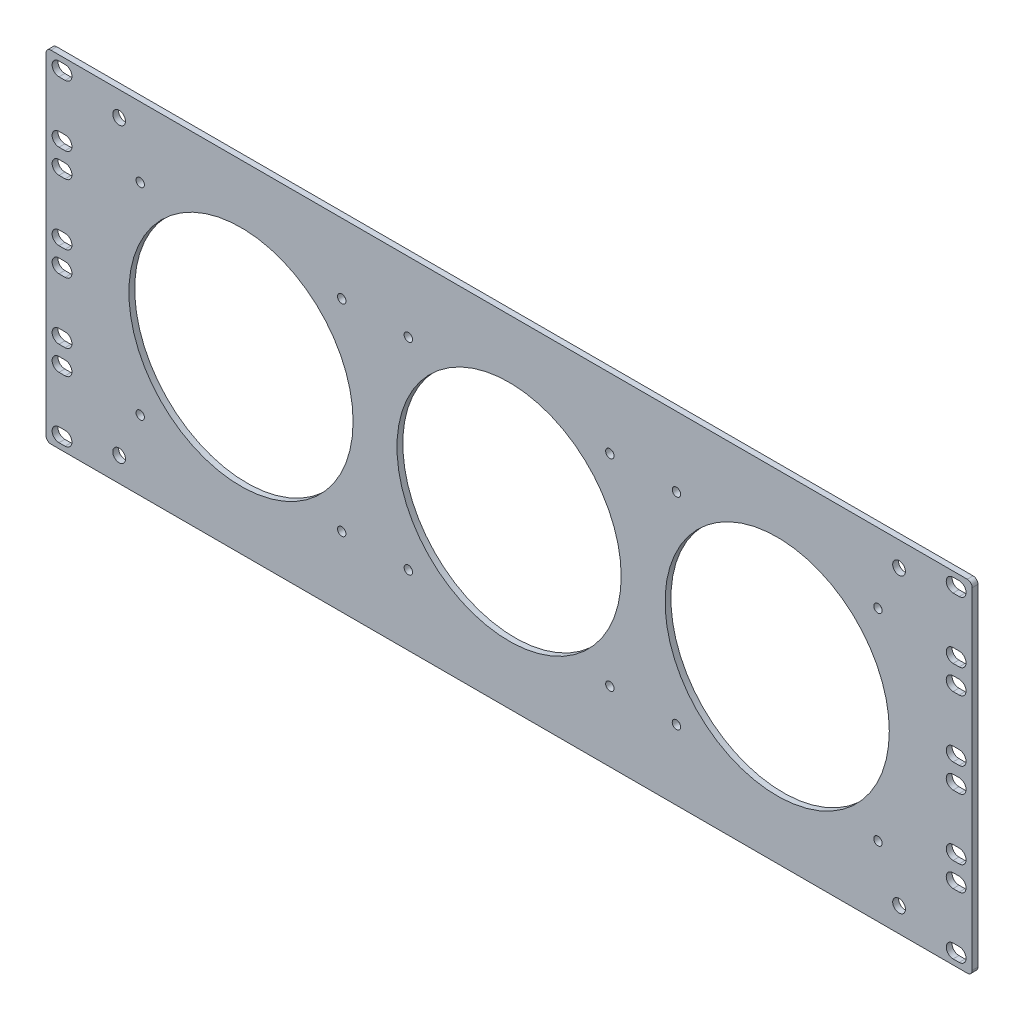
SolidWorks part; units mm, degrees
ref_plane "Plan de face" through (0, 0, 0) normal (0, 0, 1) x (1, 0, 0)
ref_plane "Plan de dessus" through (0, 0, 0) normal (0, 1, 0) x (1, 0, 0)
ref_plane "Plan de droite" through (0, 0, 0) normal (1, 0, 0) x (0, 0, -1)
sketch "Esquisse1" plane through (0, 0, 0) normal (0, 0, 1) x (1, 0, 0)
  line L1 (241.3, -88.9) -> (-241.3, -88.9)
  line L2 (241.3, -88.9) -> (241.3, 88.9)
  line L3 (241.3, 88.9) -> (-241.3, 88.9)
  line L4 (-241.3, -88.9) -> (-241.3, 88.9)
  line L5 (241.3, -88.9) -> (-241.3, 88.9) construction
  line L6 (241.3, 88.9) -> (-241.3, -88.9) construction
  point P0 (0, 0)
  dimension "D1" = 177.8
  dimension "D2" = 482.6
sheet metal parameters "Tôlerie 1" thickness 3.0378 parameters "D1"=0.0254, "Epaisseur"=3.0378
base flange "Tôle de base pliée1" sketch "Esquisse1" thickness 3.0378 reverse thickness direction no parameters "D1"=0.0254
sketch "Esquisse4" plane through (0, 0, 0) normal (0, 0, 1) x (1, 0, 0)
  line L0 (-234.5362, -82.55) -> (-231.3612, -82.55) construction
  line L1 (232.9487, -82.55) -> (-232.9487, -82.55) construction
  line L2 (232.9487, -82.55) -> (232.9487, 82.55) construction
  line L3 (232.9487, 82.55) -> (-232.9487, 82.55) construction
  line L4 (-232.9487, -82.55) -> (-232.9487, 82.55) construction
  line L5 (232.9487, -82.55) -> (-232.9487, 82.55) construction
  line L6 (232.9487, 82.55) -> (-232.9487, -82.55) construction
  line L7 (-234.5362, -78.9781) -> (-231.3612, -78.9781)
  line L8 (-234.5362, -86.1219) -> (-231.3612, -86.1219)
  line L9 (-234.5362, 82.55) -> (-231.3612, 82.55) construction
  line L10 (-234.5362, 86.1219) -> (-231.3612, 86.1219)
  line L11 (-234.5362, 78.9781) -> (-231.3612, 78.9781)
  line L12 (231.3612, 82.55) -> (234.5362, 82.55) construction
  line L13 (231.3612, 86.1219) -> (234.5362, 86.1219)
  line L14 (231.3612, 78.9781) -> (234.5362, 78.9781)
  line L15 (231.3612, -82.55) -> (234.5362, -82.55) construction
  line L16 (231.3612, -78.9781) -> (234.5362, -78.9781)
  line L17 (231.3612, -86.1219) -> (234.5362, -86.1219)
  line L18 (-234.5362, -38.1) -> (-231.3612, -38.1) construction
  line L19 (-234.5362, -34.5281) -> (-231.3612, -34.5281)
  line L20 (-234.5362, -41.6719) -> (-231.3612, -41.6719)
  line L21 (-234.5362, -50.8) -> (-231.3612, -50.8) construction
  line L22 (-234.5362, -47.2281) -> (-231.3612, -47.2281)
  line L23 (-234.5362, -54.3719) -> (-231.3612, -54.3719)
  line L24 (231.3612, -50.8) -> (234.5362, -50.8) construction
  line L25 (231.3612, -47.2281) -> (234.5362, -47.2281)
  line L26 (231.3612, -54.3719) -> (234.5362, -54.3719)
  line L27 (231.3612, -38.1) -> (234.5362, -38.1) construction
  line L28 (231.3612, -34.5281) -> (234.5362, -34.5281)
  line L29 (231.3612, -41.6719) -> (234.5362, -41.6719)
  line L30 (232.9487, -38.1) -> (232.9487, 82.55) construction
  line L31 (-234.5362, 6.35) -> (-231.3612, 6.35) construction
  line L32 (-234.5362, 9.9219) -> (-231.3612, 9.9219)
  line L33 (-234.5362, 2.7781) -> (-231.3612, 2.7781)
  line L34 (-234.5362, -6.35) -> (-231.3612, -6.35) construction
  line L35 (-234.5362, -2.7781) -> (-231.3612, -2.7781)
  line L36 (-234.5362, -9.9219) -> (-231.3612, -9.9219)
  line L37 (231.3612, 50.8) -> (234.5362, 50.8) construction
  line L38 (231.3612, 54.3719) -> (234.5362, 54.3719)
  line L39 (231.3612, 47.2281) -> (234.5362, 47.2281)
  line L40 (231.3612, 38.1) -> (234.5362, 38.1) construction
  line L41 (231.3612, 41.6719) -> (234.5362, 41.6719)
  line L42 (231.3612, 34.5281) -> (234.5362, 34.5281)
  line L43 (-234.5362, 50.8) -> (-231.3612, 50.8) construction
  line L44 (-234.5362, 54.3719) -> (-231.3612, 54.3719)
  line L45 (-234.5362, 47.2281) -> (-231.3612, 47.2281)
  line L46 (-234.5362, 38.1) -> (-231.3612, 38.1) construction
  line L47 (-234.5362, 41.6719) -> (-231.3612, 41.6719)
  line L48 (-234.5362, 34.5281) -> (-231.3612, 34.5281)
  line L49 (231.3612, 6.35) -> (234.5362, 6.35) construction
  line L50 (231.3612, 9.9219) -> (234.5362, 9.9219)
  line L51 (231.3612, 2.7781) -> (234.5362, 2.7781)
  line L52 (231.3612, -6.35) -> (234.5362, -6.35) construction
  line L53 (231.3612, -2.7781) -> (234.5362, -2.7781)
  line L54 (231.3612, -9.9219) -> (234.5362, -9.9219)
  arc A0 (-234.5362, -78.9781) -> (-234.5362, -86.1219) centre (-234.5362, -82.55) ccw
  arc A1 (-231.3612, -86.1219) -> (-231.3612, -78.9781) centre (-231.3612, -82.55) ccw
  arc A2 (-234.5362, 86.1219) -> (-234.5362, 78.9781) centre (-234.5362, 82.55) ccw
  arc A3 (-231.3612, 78.9781) -> (-231.3612, 86.1219) centre (-231.3612, 82.55) ccw
  arc A4 (231.3612, 86.1219) -> (231.3612, 78.9781) centre (231.3612, 82.55) ccw
  arc A5 (234.5362, 78.9781) -> (234.5362, 86.1219) centre (234.5362, 82.55) ccw
  arc A6 (231.3612, -78.9781) -> (231.3612, -86.1219) centre (231.3612, -82.55) ccw
  arc A7 (234.5362, -86.1219) -> (234.5362, -78.9781) centre (234.5362, -82.55) ccw
  arc A8 (-234.5362, -34.5281) -> (-234.5362, -41.6719) centre (-234.5362, -38.1) ccw
  arc A9 (-231.3612, -41.6719) -> (-231.3612, -34.5281) centre (-231.3612, -38.1) ccw
  arc A10 (-234.5362, -47.2281) -> (-234.5362, -54.3719) centre (-234.5362, -50.8) ccw
  arc A11 (-231.3612, -54.3719) -> (-231.3612, -47.2281) centre (-231.3612, -50.8) ccw
  arc A12 (231.3612, -47.2281) -> (231.3612, -54.3719) centre (231.3612, -50.8) ccw
  arc A13 (234.5362, -54.3719) -> (234.5362, -47.2281) centre (234.5362, -50.8) ccw
  arc A14 (231.3612, -34.5281) -> (231.3612, -41.6719) centre (231.3612, -38.1) ccw
  arc A15 (234.5362, -41.6719) -> (234.5362, -34.5281) centre (234.5362, -38.1) ccw
  arc A16 (-234.5362, 9.9219) -> (-234.5362, 2.7781) centre (-234.5362, 6.35) ccw
  arc A17 (-231.3612, 2.7781) -> (-231.3612, 9.9219) centre (-231.3612, 6.35) ccw
  arc A18 (-234.5362, -2.7781) -> (-234.5362, -9.9219) centre (-234.5362, -6.35) ccw
  arc A19 (-231.3612, -9.9219) -> (-231.3612, -2.7781) centre (-231.3612, -6.35) ccw
  arc A20 (231.3612, 54.3719) -> (231.3612, 47.2281) centre (231.3612, 50.8) ccw
  arc A21 (234.5362, 47.2281) -> (234.5362, 54.3719) centre (234.5362, 50.8) ccw
  arc A22 (231.3612, 41.6719) -> (231.3612, 34.5281) centre (231.3612, 38.1) ccw
  arc A23 (234.5362, 34.5281) -> (234.5362, 41.6719) centre (234.5362, 38.1) ccw
  arc A24 (-234.5362, 54.3719) -> (-234.5362, 47.2281) centre (-234.5362, 50.8) ccw
  arc A25 (-231.3612, 47.2281) -> (-231.3612, 54.3719) centre (-231.3612, 50.8) ccw
  arc A26 (-234.5362, 41.6719) -> (-234.5362, 34.5281) centre (-234.5362, 38.1) ccw
  arc A27 (-231.3612, 34.5281) -> (-231.3612, 41.6719) centre (-231.3612, 38.1) ccw
  arc A28 (231.3612, 9.9219) -> (231.3612, 2.7781) centre (231.3612, 6.35) ccw
  arc A29 (234.5362, 2.7781) -> (234.5362, 9.9219) centre (234.5362, 6.35) ccw
  arc A30 (231.3612, -2.7781) -> (231.3612, -9.9219) centre (231.3612, -6.35) ccw
  arc A31 (234.5362, -9.9219) -> (234.5362, -2.7781) centre (234.5362, -6.35) ccw
  point P0 (0, 0)
  point P8 (-232.9487, -82.55)
  point P14 (-232.9487, 82.55)
  point P21 (232.9487, 82.55)
  point P28 (232.9487, -82.55)
  point P36 (-232.9487, -38.1)
  point P42 (-232.9487, -50.8)
  point P49 (232.9487, -50.8)
  point P56 (232.9487, -38.1)
  point P65 (-232.9487, 6.35)
  point P71 (-232.9487, -6.35)
  point P79 (232.9487, 50.8)
  point P86 (232.9487, 38.1)
  point P93 (-232.9487, 50.8)
  point P99 (-232.9487, 38.1)
  point P107 (232.9487, 6.35)
  point P113 (232.9487, -6.35)
  dimension "D2" = 3.5719
  dimension "D1" = 465.8975
  dimension "D3" = 3.175
  dimension "D4" = 12.7
  dimension "D5" = 31.75
  dimension "D6" = 31.75
  dimension "D7" = 12.7
  dimension "D8" = 31.75
  dimension "D9" = 12.7
  dimension "D10" = 165.1
  dimension "D11" = 31.75
  dimension "D12" = 12.7
  dimension "D13" = 31.75
  dimension "D14" = 31.75
  dimension "D15" = 31.75
  dimension "D16" = 31.75
extrude "Enlèv. mat.-Extru.1" cut sketch "Esquisse4" against normal through all normal cut yes
fillet "Congé1" radius 2.54 4 edges at (241.3, 88.9, -1.5189) (241.3, -88.9, -1.5189) (-241.3, 88.9, -1.5189) (-241.3, -88.9, -1.5189)
sketch "Esquisse5" plane through (0, 0, 0) normal (0, 0, 1) x (1, 0, 0)
  line L0 (0, 0) -> (139.7, 0) construction
  line L1 (0, 0) -> (-139.7, 0) construction
  circle A0 centre (0, 0) radius 58.42
  circle A1 centre (-139.7, 0) radius 58.42
  circle A2 centre (139.7, 0) radius 58.42
  dimension "D3" = 116.84
  dimension "D1" = 139.7
  dimension "D2" = 139.7
extrude "Enlèv. mat.-Extru.2" cut sketch "Esquisse5" against normal through all normal cut yes
sketch "Esquisse6" plane through (0, 0, -3.0378) normal (0, 0, -1) x (-1, 0, 0)
  circle A0 centre (-192.2, 52.5) radius 2.1844
  circle A1 centre (-87.2, 52.5) radius 2.1844
  circle A2 centre (-52.5, 52.5) radius 2.1844
  circle A4 centre (-87.2, -52.5) radius 2.1844
  circle A5 centre (-52.5, -52.5) radius 2.1844
  circle A6 centre (-192.2, -52.5) radius 2.1844
  circle A7 centre (52.5, 52.5) radius 2.1844
  circle A8 centre (52.5, -52.5) radius 2.1844
  circle A9 centre (87.2, -52.5) radius 2.1844
  circle A10 centre (87.2, 52.5) radius 2.1844
  circle A11 centre (192.2, 52.5) radius 2.1844
  circle A12 centre (192.2, -52.5) radius 2.1844
  dimension "D1" = 4.3688
extrude "Enlèv. mat.-Extru.3" cut sketch "Esquisse6" against normal through all normal cut yes
sketch "Esquisse7" plane through (0, 0, 0) normal (0, 0, 1) x (1, 0, 0)
  line L1 (-203.2, -76.2) -> (203.2, -76.2) construction
  line L2 (-203.2, -76.2) -> (-203.2, 76.2) construction
  line L3 (-203.2, 76.2) -> (203.2, 76.2) construction
  line L4 (203.2, -76.2) -> (203.2, 76.2) construction
  line L5 (-203.2, -76.2) -> (203.2, 76.2) construction
  line L6 (-203.2, 76.2) -> (203.2, -76.2) construction
  circle A0 centre (-203.2, 76.2) radius 3.3179
  circle A1 centre (-203.2, -76.2) radius 3.3179
  circle A2 centre (203.2, -76.2) radius 3.3179
  circle A3 centre (203.2, 76.2) radius 3.3179
  point P0 (0, 0)
  dimension "D3" = 6.6357
  dimension "D1" = 152.4
  dimension "D2" = 406.4
extrude "Enlèv. mat.-Extru.4" cut sketch "Esquisse7" against normal through all normal cut yes
flat pattern "Etat déplié1" [suppressed]
sketch "Lignes de pliage1" plane through (0, 0, 0) normal (0, 1, 0) x (1, 0, 0)
sketch3d "Cube de visualisation1" [suppressed]
  line L0 (241.3, -43.5, 0) -> (-241.3, -43.5, 0) construction
  line L1 (241.3, 43.5, 0) -> (-241.3, 43.5, 0) construction
  line L2 (241.3, -43.5, 0) -> (241.3, 43.5, 0) construction
  line L3 (-241.3, -43.5, 0) -> (-241.3, 43.5, 0) construction
